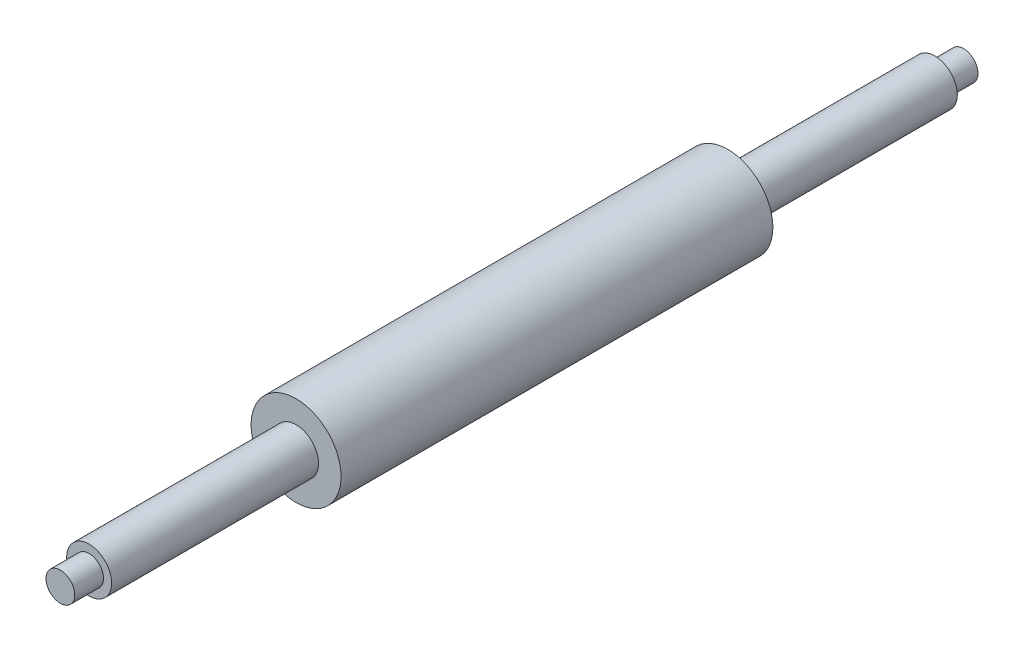
SolidWorks part; units mm, degrees
ref_plane "Front Plane" through (0, 0, 0) normal (0, 0, 1) x (1, 0, 0)
ref_plane "Top Plane" through (0, 0, 0) normal (0, 1, 0) x (1, 0, 0)
ref_plane "Right Plane" through (0, 0, 0) normal (1, 0, 0) x (0, 0, -1)
sketch "Sketch3" plane through (0, 0, 0) normal (0, 0, 1) x (1, 0, 0)
  circle A0 centre (0, 0) radius 4
  circle A1 centre (0, 0) radius 6.25
  circle A2 centre (0, 0) radius 12.5
  dimension "D1" = 25
  dimension "D2" = 12.5
  dimension "D3" = 8
extrude "Boss-Extrude1" add sketch "Sketch3" along normal mid plane 120 contours A2 A1 region at (-12.1464, 0, 0)
extrude "Boss-Extrude2" add sketch "Sketch3<3>" along normal mid plane 235 contours A1 A0 region at (-6.0732, 0, 0)
sketch "Sketch3<3>" plane through (0, 0, 0) normal (0, 0, 1) x (1, 0, 0) same geometry as "Sketch3"
extrude "Boss-Extrude3" add sketch "Sketch3<4>" along normal mid plane 251 contours A0 region at (0, 0, 0)
sketch "Sketch3<4>" plane through (0, 0, 0) normal (0, 0, 1) x (1, 0, 0) same geometry as "Sketch3"
sketch "Sketch5" plane through (0, 0, 0) normal (1, 0, 0) x (0, 0, -1)
  circle A0 centre (0, 0) radius 7.5
  dimension "D1" = 15
extrude "Cut-Extrude4" cut sketch "Sketch5" against normal through all
